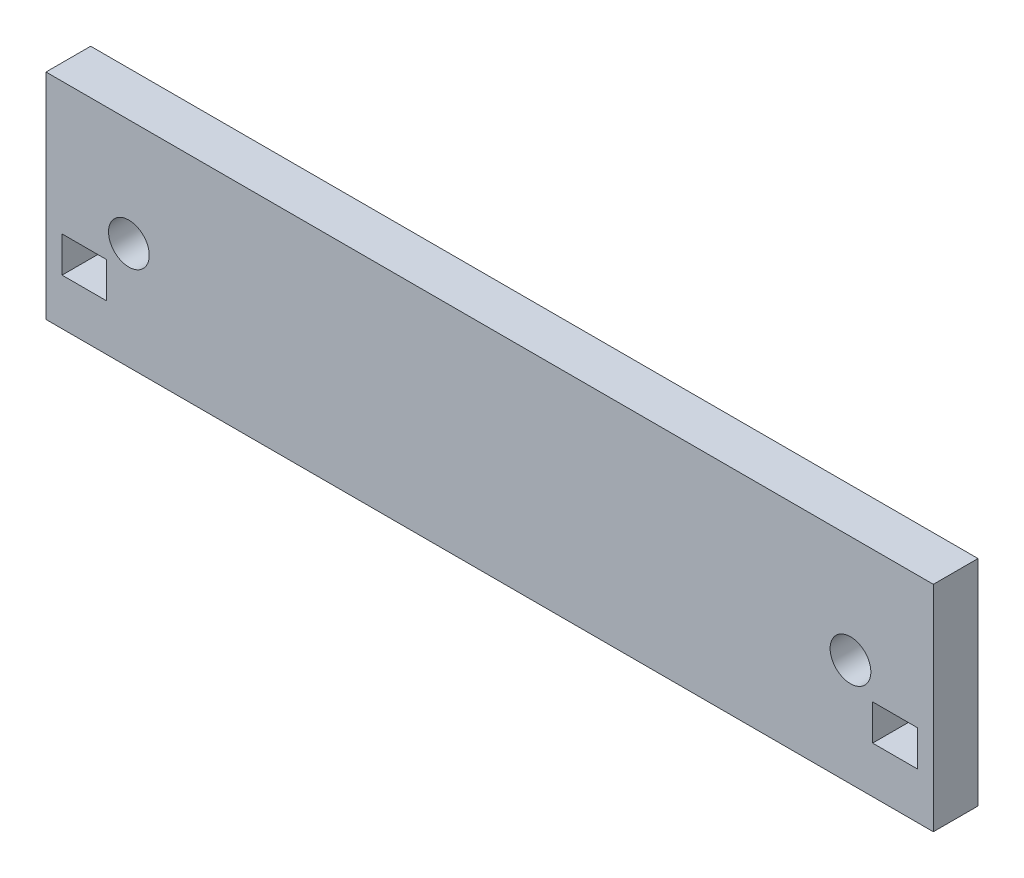
SolidWorks part; units mm, degrees
material "Beech"
ref_plane "Front Plane" through (0, 0, 0) normal (0, 0, 1) x (1, 0, 0)
ref_plane "Top Plane" through (0, 0, 0) normal (0, 1, 0) x (1, 0, 0)
ref_plane "Right Plane" through (0, 0, 0) normal (1, 0, 0) x (0, 0, -1)
sketch "Sketch1" plane through (0, 0, 0) normal (0, 0, 1) x (1, 0, 0)
  line L0 (0, -1000) -> (0, 49000) construction
  line L1 (-18.034, -3.81) -> (13.5128, -3.81)
  line L2 (-18.034, -3.81) -> (-18.034, 3.81)
  line L3 (-18.034, 3.81) -> (13.5128, 3.81)
  line L4 (13.5128, -3.81) -> (13.5128, 3.81)
  line L5 (12.9413, -0.889) -> (13.5128, -0.889) construction
  line L6 (10.5664, -3.81) -> (10.5664, 0) construction
  line L7 (-17.4625, -2.159) -> (-15.875, -2.159)
  line L8 (-17.4625, -2.159) -> (-17.4625, -0.889)
  line L9 (-17.4625, -0.889) -> (-15.875, -0.889)
  line L10 (-15.875, -2.159) -> (-15.875, -0.889)
  line L11 (11.3538, -2.159) -> (11.3538, -0.889)
  line L12 (12.9413, -0.889) -> (11.3538, -0.889)
  line L13 (12.9413, -2.159) -> (12.9413, -0.889)
  line L14 (12.9413, -2.159) -> (11.3538, -2.159)
  line L15 (-1000, 0) -> (49000, 0) construction
  line L16 (10.5664, 0) -> (10.5664, 3.81) construction
  line L17 (-17.4625, -0.889) -> (-18.034, -0.889) construction
  circle A0 centre (-15.0876, 0) radius 0.7239
  circle A1 centre (10.5664, 0) radius 0.7239
  point P0 (0, 0)
  dimension "D6" = 1.4478
  dimension "D7" = 0.7874
  dimension "D1" = 0.5715
  dimension "D2" = 7.62
  dimension "D3" = 1.5875
  dimension "D4" = 15.875
  dimension "D5" = 1.27
  dimension "D8" = 0.7874
  dimension "D9" = 25.654
  dimension "D10" = 4.699
extrude "Boss-Extrude1" add sketch "Sketch1" along normal blind 1.5875
move or copy body "Body-Move/Copy1" [suppressed] bodies to move or copy 101
